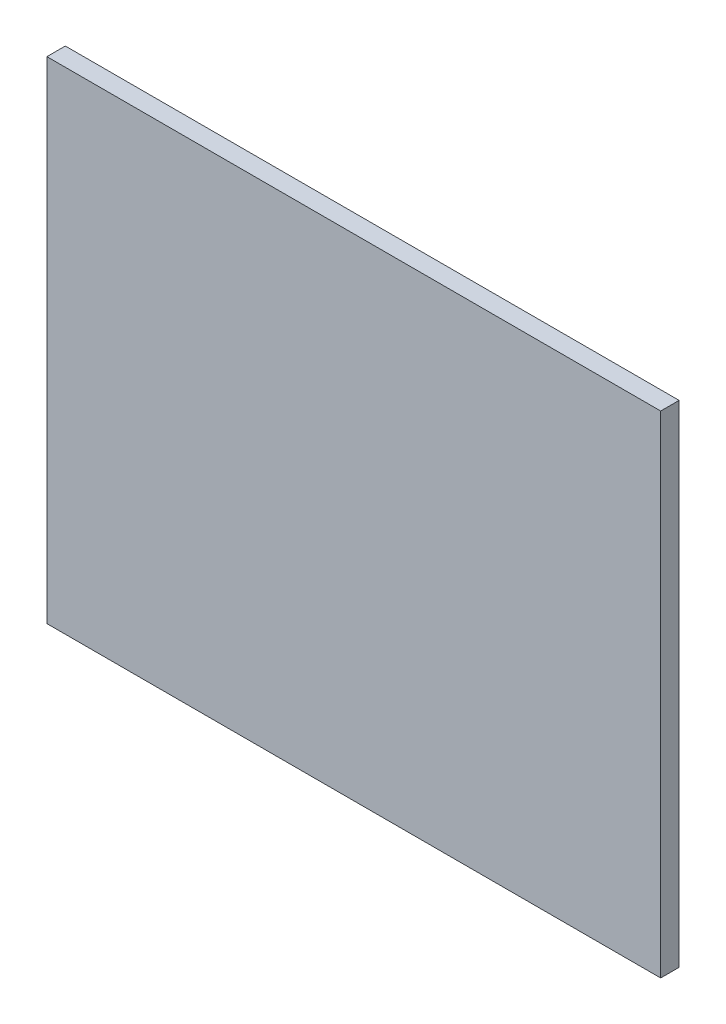
SolidWorks part; units mm, degrees
ref_plane "Přední rovina" through (0, 0, 0) normal (0, 0, 1) x (1, 0, 0)
ref_plane "Horní rovina" through (0, 0, 0) normal (0, 1, 0) x (1, 0, 0)
ref_plane "Pravá rovina" through (0, 0, 0) normal (1, 0, 0) x (0, 0, -1)
sketch "Skica1" plane through (0, 0, 0) normal (0, 0, 1) x (1, 0, 0)
  line L1 (0, 0) -> (100, 0)
  line L2 (0, 0) -> (0, 80)
  line L3 (0, 80) -> (100, 80)
  line L4 (100, 0) -> (100, 80)
  dimension "D1" = 100
  dimension "D2" = 80
extrude "Přidat vysunutím1" add sketch "Skica1" along normal blind 3
